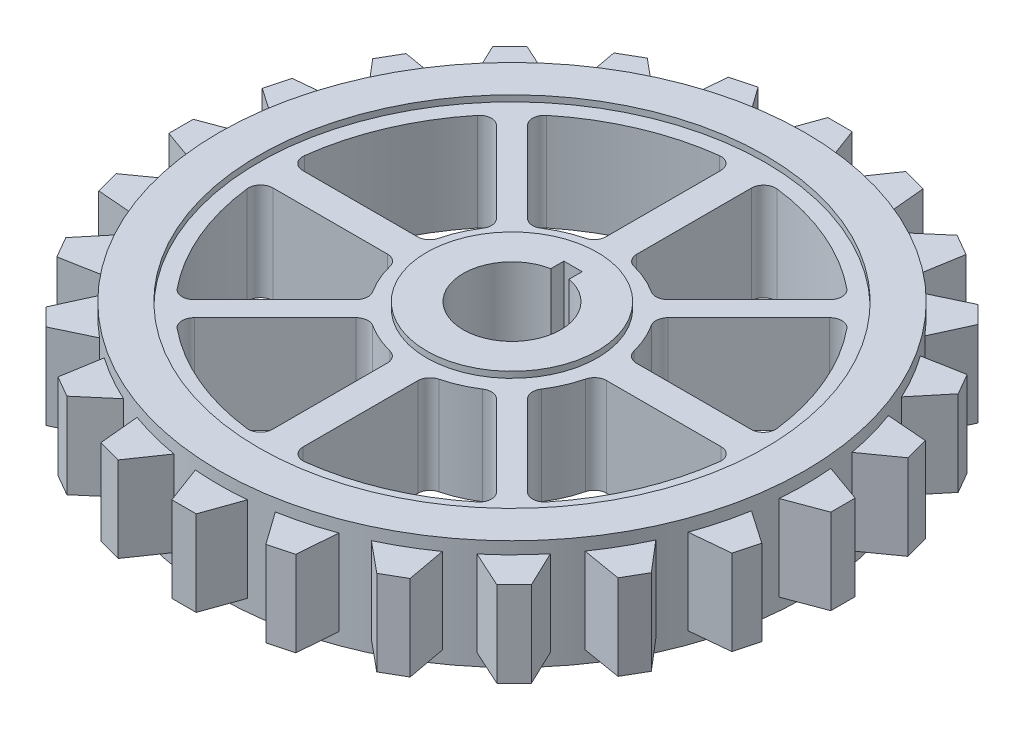
SolidWorks part; units mm, degrees
ref_plane "Front Plane" through (0, 0, 0) normal (0, 0, 1) x (1, 0, 0)
ref_plane "Top Plane" through (0, 0, 0) normal (0, 1, 0) x (1, 0, 0)
ref_plane "Right Plane" through (0, 0, 0) normal (1, 0, 0) x (0, 0, -1)
sketch "Sketch1" plane through (0, 0, 0) normal (0, 1, 0) x (1, 0, 0)
  line L0 (-1.5, 7.8581) -> (-1.5, 10)
  line L1 (-1.5, 10) -> (1.5, 10)
  line L2 (1.5, 10) -> (1.5, 7.8581)
  line L3 (-1.5, 54.025) -> (1.7546, 54.025)
  line L4 (1.7546, 54.025) -> (-2.2454, 54.025)
  line L5 (-2.2454, 54.025) -> (-4.4499, 47.8184)
  line L6 (1.7546, 54.025) -> (4.0554, 47.8535)
  line L7 (15.6775, 51.73) -> (16.3026, 45.1733)
  line L8 (15.6775, 51.73) -> (11.8138, 52.7653)
  line L9 (11.8138, 52.7653) -> (8.0781, 47.3407)
  line L10 (28.532, 45.9097) -> (27.4388, 39.4146)
  line L11 (28.532, 45.9097) -> (25.0679, 47.9097)
  line L12 (25.0679, 47.9097) -> (20.0555, 43.6369)
  line L13 (39.4421, 36.9608) -> (36.7051, 30.9699)
  line L14 (39.4421, 36.9608) -> (36.6137, 39.7892)
  line L15 (36.6137, 39.7892) -> (30.6662, 36.9593)
  line L16 (47.6643, 25.493) -> (43.47, 20.4147)
  line L17 (47.6643, 25.493) -> (45.6643, 28.9571)
  line L18 (45.6643, 28.9571) -> (39.187, 27.7629)
  line L19 (52.6383, 12.2879) -> (47.2725, 8.4682)
  line L20 (52.6383, 12.2879) -> (51.603, 16.1516)
  line L21 (51.603, 16.1516) -> (45.0373, 16.6746)
  line L22 (54.025, -1.7546) -> (47.8535, -4.0554)
  line L23 (54.025, -1.7546) -> (54.025, 2.2454)
  line L24 (54.025, 2.2454) -> (47.8184, 4.4499)
  line L25 (51.73, -15.6775) -> (45.1733, -16.3026)
  line L26 (51.73, -15.6775) -> (52.7653, -11.8138)
  line L27 (52.7653, -11.8138) -> (47.3407, -8.0781)
  line L28 (45.9097, -28.532) -> (39.4146, -27.4388)
  line L29 (45.9097, -28.532) -> (47.9097, -25.0679)
  line L30 (47.9097, -25.0679) -> (43.6369, -20.0555)
  line L31 (36.9608, -39.4421) -> (30.9699, -36.7051)
  line L32 (36.9608, -39.4421) -> (39.7892, -36.6137)
  line L33 (39.7892, -36.6137) -> (36.9593, -30.6662)
  line L34 (25.493, -47.6643) -> (20.4147, -43.47)
  line L35 (25.493, -47.6643) -> (28.9571, -45.6643)
  line L36 (28.9571, -45.6643) -> (27.7629, -39.187)
  line L37 (12.2879, -52.6383) -> (8.4682, -47.2725)
  line L38 (12.2879, -52.6383) -> (16.1516, -51.603)
  line L39 (16.1516, -51.603) -> (16.6746, -45.0373)
  line L40 (-1.7546, -54.025) -> (-4.0554, -47.8535)
  line L41 (-1.7546, -54.025) -> (2.2454, -54.025)
  line L42 (2.2454, -54.025) -> (4.4499, -47.8184)
  line L43 (-15.6775, -51.73) -> (-16.3026, -45.1733)
  line L44 (-15.6775, -51.73) -> (-11.8138, -52.7653)
  line L45 (-11.8138, -52.7653) -> (-8.0781, -47.3407)
  line L46 (-28.532, -45.9097) -> (-27.4388, -39.4146)
  line L47 (-28.532, -45.9097) -> (-25.0679, -47.9097)
  line L48 (-25.0679, -47.9097) -> (-20.0555, -43.6369)
  line L49 (-39.4421, -36.9608) -> (-36.7051, -30.9699)
  line L50 (-39.4421, -36.9608) -> (-36.6137, -39.7892)
  line L51 (-36.6137, -39.7892) -> (-30.6662, -36.9593)
  line L52 (-47.6643, -25.493) -> (-43.47, -20.4147)
  line L53 (-47.6643, -25.493) -> (-45.6643, -28.9571)
  line L54 (-45.6643, -28.9571) -> (-39.187, -27.7629)
  line L55 (-52.6383, -12.2879) -> (-47.2725, -8.4682)
  line L56 (-52.6383, -12.2879) -> (-51.603, -16.1516)
  line L57 (-51.603, -16.1516) -> (-45.0373, -16.6746)
  line L58 (-54.025, 1.7546) -> (-47.8535, 4.0554)
  line L59 (-54.025, 1.7546) -> (-54.025, -2.2454)
  line L60 (-54.025, -2.2454) -> (-47.8184, -4.4499)
  line L61 (-51.73, 15.6775) -> (-45.1733, 16.3026)
  line L62 (-51.73, 15.6775) -> (-52.7653, 11.8138)
  line L63 (-52.7653, 11.8138) -> (-47.3407, 8.0781)
  line L64 (-45.9097, 28.532) -> (-39.4146, 27.4388)
  line L65 (-45.9097, 28.532) -> (-47.9097, 25.0679)
  line L66 (-47.9097, 25.0679) -> (-43.6369, 20.0555)
  line L67 (-36.9608, 39.4421) -> (-30.9699, 36.7051)
  line L68 (-36.9608, 39.4421) -> (-39.7892, 36.6137)
  line L69 (-39.7892, 36.6137) -> (-36.9593, 30.6662)
  line L70 (-25.493, 47.6643) -> (-20.4147, 43.47)
  line L71 (-25.493, 47.6643) -> (-28.9571, 45.6643)
  line L72 (-28.9571, 45.6643) -> (-27.7629, 39.187)
  line L73 (-12.2879, 52.6383) -> (-8.4682, 47.2725)
  line L74 (-12.2879, 52.6383) -> (-16.1516, 51.603)
  line L75 (-16.1516, 51.603) -> (-16.6746, 45.0373)
  line L76 (0, 0) -> (0, 68.1742) construction
  line L77 (0, 68.1742) -> (0, -67.9696) construction
  line L79 (2.5, 36.7505) -> (2.5, 17.9444)
  line L80 (17.9555, 2.4554) -> (36.756, 2.4554)
  line L82 (11.5263, 14.0776) -> (24.7664, 27.3177)
  line L83 (0, 0) -> (116.3409, 0) construction
  line L84 (14.0776, 11.5263) -> (27.3177, 24.7664)
  line L85 (116.3409, 0) -> (-87.7787, 0) construction
  line L86 (38.6489, 2.4554) -> (38.9477, 2.4554)
  line L88 (14.0776, -11.5263) -> (27.3177, -24.7664)
  line L89 (2.5, -36.7505) -> (2.5, -17.9444)
  line L90 (11.5263, -14.0776) -> (24.7664, -27.3177)
  line L91 (-11.5263, -14.0776) -> (-24.7664, -27.3177)
  line L92 (-2.5, -36.7505) -> (-2.5, -17.9444)
  line L93 (-17.9555, -2.4554) -> (-36.756, -2.4554)
  line L94 (-38.6489, -2.4554) -> (-38.9477, -2.4554)
  line L95 (-14.0776, -11.5263) -> (-27.3177, -24.7664)
  line L96 (-17.9555, 2.4554) -> (-36.756, 2.4554)
  line L97 (-38.6489, 2.4554) -> (-38.9477, 2.4554)
  line L98 (-14.0776, 11.5263) -> (-27.3177, 24.7664)
  line L99 (-2.5, 36.7505) -> (-2.5, 17.9444)
  line L100 (-11.5263, 14.0776) -> (-24.7664, 27.3177)
  line L102 (17.9555, -2.4554) -> (36.756, -2.4554)
  arc A0 (-1.5, 7.8581) -> (1.5, 7.8581) centre (0, 0) ccw
  circle A1 centre (0, 0) radius 14
  arc A2 (9.0189, 13.817) -> (4.0135, 16.0044) centre (0, 0) ccw
  circle A4 centre (0, 0) radius 48.025
  circle A5 centre (0, 0) radius 41.525
  arc A6 (24.6136, 30.284) -> (4.7431, 38.7357) centre (0, 0) ccw
  circle A7 centre (0, 0) radius 16.5 construction
  arc A10 (16.0144, 3.9737) -> (13.817, 9.0189) centre (0, 0) ccw
  arc A11 (38.7414, 4.696) -> (30.284, 24.6136) centre (0, 0) ccw
  arc A12 (16.0144, -3.9737) -> (13.817, -9.0189) centre (0, 0) cw
  arc A13 (38.7414, -4.696) -> (30.284, -24.6136) centre (0, 0) cw
  arc A14 (9.0189, -13.817) -> (4.0135, -16.0044) centre (0, 0) cw
  arc A15 (24.6136, -30.284) -> (4.7431, -38.7357) centre (0, 0) cw
  arc A16 (-24.6136, -30.284) -> (-4.7431, -38.7357) centre (0, 0) ccw
  arc A17 (-9.0189, -13.817) -> (-4.0135, -16.0044) centre (0, 0) ccw
  arc A18 (-38.7414, -4.696) -> (-30.284, -24.6136) centre (0, 0) ccw
  arc A19 (-16.0144, -3.9737) -> (-13.817, -9.0189) centre (0, 0) ccw
  arc A20 (-16.0144, 3.9737) -> (-13.817, 9.0189) centre (0, 0) cw
  arc A21 (-38.7414, 4.696) -> (-30.284, 24.6136) centre (0, 0) cw
  arc A22 (-9.0189, 13.817) -> (-4.0135, 16.0044) centre (0, 0) cw
  arc A23 (-24.6136, 30.284) -> (-4.7431, 38.7357) centre (0, 0) cw
  arc A24 (-30.284, 24.6136) -> (-27.3177, 24.7664) centre (-28.7319, 23.3522) cw
  arc A25 (-24.6136, 30.284) -> (-24.7664, 27.3177) centre (-23.3522, 28.7319) ccw
  arc A26 (-9.0189, 13.817) -> (-11.5263, 14.0776) centre (-10.1121, 15.4918) cw
  arc A27 (-4.0135, 16.0044) -> (-2.5, 17.9444) centre (-4.5, 17.9444) ccw
  arc A28 (-2.5, 36.7505) -> (-4.7431, 38.7357) centre (-4.5, 36.7505) ccw
  arc A29 (2.5, 17.9444) -> (4.0135, 16.0044) centre (4.5, 17.9444) ccw
  arc A30 (2.5, 36.7505) -> (4.7431, 38.7357) centre (4.5, 36.7505) cw
  arc A31 (-2.5, -17.9444) -> (-4.0135, -16.0044) centre (-4.5, -17.9444) ccw
  arc A32 (-4.7431, -38.7357) -> (-2.5, -36.7505) centre (-4.5, -36.7505) ccw
  arc A33 (-24.7664, -27.3177) -> (-24.6136, -30.284) centre (-23.3522, -28.7319) ccw
  arc A34 (-11.5263, -14.0776) -> (-9.0189, -13.817) centre (-10.1121, -15.4918) cw
  arc A35 (-38.7414, 4.696) -> (-36.756, 2.4554) centre (-36.756, 4.4554) ccw
  arc A36 (13.817, -9.0189) -> (14.0776, -11.5263) centre (15.4918, -10.1121) ccw
  arc A37 (30.284, -24.6136) -> (27.3177, -24.7664) centre (28.7319, -23.3522) cw
  arc A38 (24.6136, -30.284) -> (24.7664, -27.3177) centre (23.3522, -28.7319) ccw
  arc A39 (9.0189, -13.817) -> (11.5263, -14.0776) centre (10.1121, -15.4918) cw
  arc A40 (4.0135, -16.0044) -> (2.5, -17.9444) centre (4.5, -17.9444) ccw
  arc A41 (2.5, -36.7505) -> (4.7431, -38.7357) centre (4.5, -36.7505) ccw
  arc A42 (-14.0776, -11.5263) -> (-13.817, -9.0189) centre (-15.4918, -10.1121) ccw
  arc A43 (-30.284, -24.6136) -> (-27.3177, -24.7664) centre (-28.7319, -23.3522) ccw
  arc A44 (-38.7414, -4.696) -> (-36.756, -2.4554) centre (-36.756, -4.4554) cw
  arc A45 (-17.9555, -2.4554) -> (-16.0144, -3.9737) centre (-17.9555, -4.4554) cw
  arc A46 (-16.0144, 3.9737) -> (-17.9555, 2.4554) centre (-17.9555, 4.4554) cw
  arc A47 (-13.817, 9.0189) -> (-14.0776, 11.5263) centre (-15.4918, 10.1121) ccw
  arc A48 (38.7414, 4.696) -> (36.756, 2.4554) centre (36.756, 4.4554) cw
  arc A49 (16.0144, -3.9737) -> (17.9555, -2.4554) centre (17.9555, -4.4554) cw
  arc A50 (38.7414, -4.696) -> (36.756, -2.4554) centre (36.756, -4.4554) ccw
  arc A51 (17.9555, 2.4554) -> (16.0144, 3.9737) centre (17.9555, 4.4554) cw
  arc A52 (27.3177, 24.7664) -> (30.284, 24.6136) centre (28.7319, 23.3522) cw
  arc A53 (24.7664, 27.3177) -> (24.6136, 30.284) centre (23.3522, 28.7319) ccw
  arc A54 (13.817, 9.0189) -> (14.0776, 11.5263) centre (15.4918, 10.1121) cw
  arc A55 (11.5263, 14.0776) -> (9.0189, 13.817) centre (10.1121, 15.4918) cw
  point P8 (0, 10)
  point P15 (0, 48.025)
  point P114 (0, 0)
  point P153 (-28.841, 26.2897)
  point P156 (-26.2897, 28.841)
  point P159 (-10.3217, 12.873)
  point P162 (-2.5, 16.3095)
  point P165 (-2.5, 38.9448)
  point P168 (2.5, 16.3095)
  point P171 (2.5, 38.9448)
  point P174 (-2.5, -16.3095)
  point P177 (-2.5, -38.9448)
  point P180 (-26.2897, -28.841)
  point P183 (-10.3217, -12.873)
  point P189 (12.873, -10.3217)
  point P192 (28.841, -26.2897)
  point P195 (26.2897, -28.841)
  point P198 (10.3217, -12.873)
  point P201 (2.5, -16.3095)
  point P204 (2.5, -38.9448)
  point P207 (-12.873, -10.3217)
  point P210 (-28.841, -26.2897)
  point P216 (-16.3163, -2.4554)
  point P219 (-16.3163, 2.4554)
  point P222 (-12.873, 10.3217)
  point P228 (16.3163, -2.4554)
  point P232 (16.3163, 2.4554)
  point P235 (28.841, 26.2897)
  point P236 (0, 0)
  point P239 (26.2897, 28.841)
  point P242 (12.873, 10.3217)
  point P245 (10.3217, 12.873)
  dimension "D1" = 16
  dimension "D2" = 28
  dimension "D6" = 40
  dimension "D7" = 6
  dimension "D8" = 6.5
  dimension "D9" = 2.5
  dimension "D12" = 2
  dimension "D13" = 2
  dimension "D15" = 2
  dimension "D16" = 2
  dimension "D17" = 2
  dimension "D18" = 2
  dimension "D19" = 2
  dimension "D20" = 2
  dimension "D21" = 2
  dimension "D22" = 2
  dimension "D23" = 2
  dimension "D4" = 3
  dimension "D5" = 10
  dimension "D10" = 4
  dimension "D14" = 45
  dimension "D3" = 2.5
  dimension "D11" = 24
extrude "Boss-Extrude1" add sketch "Sketch1" along normal mid plane 18 contours A4 A5 region at (5.9004, 0, -46.2921)
extrude "Boss-Extrude2" add sketch "Sketch1<8>" along normal mid plane 14 contours A4 L7 L8 L9 | A4 L10 L11 L12 | A4 L13 L14 L15 | A4 L16 L17 L18 | A4 L19 L20 L21 region at (12.8916, 0, -48.966) region at (25.1257, 0, -43.9609) region at (35.6475, 0, -35.96) region at (43.7399, 0, -25.5084) region at (48.8516, 0, -13.3185)
sketch "Sketch1<8>" plane through (0, 0, 0) normal (0, 1, 0) x (1, 0, 0) same geometry as "Sketch1"
extrude "Boss-Extrude3" add sketch "Sketch1<9>" along normal mid plane 14 contours A4 L6 L3 L4 L5 | A4 L73 L74 L75 | A4 L70 L71 L72 | A4 L67 L68 L69 | A4 L64 L65 L66 | A4 L61 L62 L63 | A4 L58 L59 L60 | A4 L55 L56 L57 | A4 L52 L53 L54 | A4 L49 L50 L51 | A4 L46 L47 L48 | A4 L43 L44 L45 | A4 L25 L26 L27 | A4 L28 L29 L30 | A4 L31 L32 L33 | A4 L34 L35 L36 | A4 L37 L38 L39 region at (-0.221, 0, -50.6341) region at (-13.3185, 0, -48.8516) region at (-25.5084, 0, -43.7399) region at (-35.96, 0, -35.6475) region at (-43.9609, 0, -25.1257) region at (-48.966, 0, -12.8916) region at (-50.6341, 0, 0.221) region at (-48.8516, 0, 13.3185) region at (48.966, 0, 12.8916) region at (-43.7399, 0, 25.5084) region at (43.9609, 0, 25.1257) region at (-35.6475, 0, 35.96) region at (35.96, 0, 35.6475) region at (-25.1257, 0, 43.9609) region at (25.5084, 0, 43.7399) region at (-12.8916, 0, 48.966) region at (13.3185, 0, 48.8516)
sketch "Sketch1<9>" plane through (0, 0, 0) normal (0, 1, 0) x (1, 0, 0) same geometry as "Sketch1"
extrude "Boss-Extrude4" add sketch "Sketch1<10>" along normal mid plane 14 contours A4 L40 L41 L42 | A4 L22 L23 L24 region at (50.6341, 0, -0.221) region at (0.221, 0, 50.6341)
sketch "Sketch1<10>" plane through (0, 0, 0) normal (0, 1, 0) x (1, 0, 0) same geometry as "Sketch1"
extrude "Boss-Extrude5" add sketch "Sketch1<11>" along normal mid plane 18 separate body contours A1 A0 L0 L1 L2 region at (-13.604, 0, 0)
sketch "Sketch1<11>" plane through (0, 0, 0) normal (0, 1, 0) x (1, 0, 0) same geometry as "Sketch1"
extrude "Boss-Extrude6" add sketch "Sketch1<12>" along normal mid plane 16 contours A5 A50 A13 A37 L88 A36 A12 A49 L102 A47 A20 A46 L96 A35 A21 A24 L98 A41 L89 A40 A14 A39 L90 A38 A15 A28 L99 A27 A22 A26 L100 A25 A23 A1 L91 A34 region at (-40.3505, 0, 0)
sketch "Sketch1<12>" plane through (0, 0, 0) normal (0, 1, 0) x (1, 0, 0) same geometry as "Sketch1"
